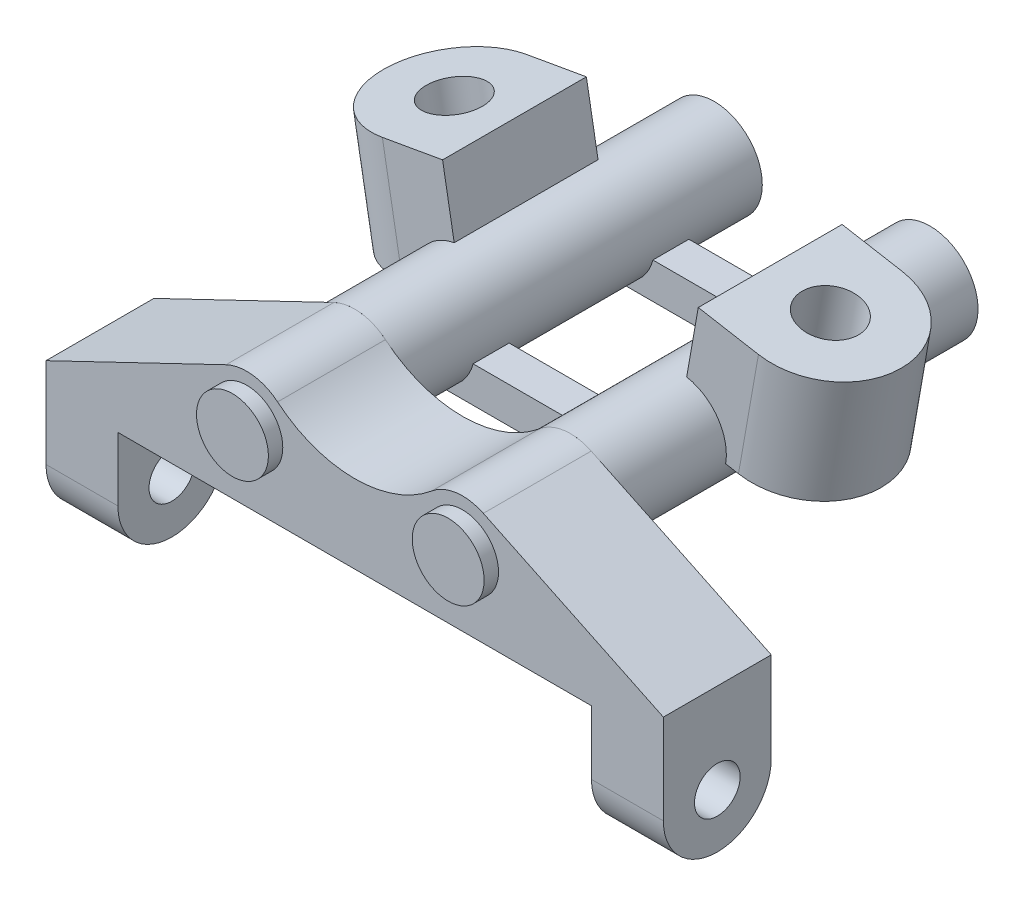
SolidWorks part; units mm, degrees
ref_plane "Front Plane" through (0, 0, 0) normal (0, 0, 1) x (1, 0, 0)
ref_plane "Top Plane" through (0, 0, 0) normal (0, 1, 0) x (1, 0, 0)
ref_plane "Right Plane" through (0, 0, 0) normal (1, 0, 0) x (0, 0, -1)
sketch "Sketch1" plane through (0, 0, 0) normal (0, 0, 1) x (1, 0, 0)
  line L0 (-42.926, -44) -> (-32.926, -44)
  line L1 (-32.926, -44) -> (-32.926, -28.7102)
  line L2 (42.926, -24) -> (42.926, -44)
  line L3 (42.926, -44) -> (32.926, -44)
  line L4 (32.926, -44) -> (32.926, -28.7102)
  line L6 (-42.926, -24) -> (-17.8935, -11.9775)
  line L7 (42.926, -24) -> (17.8912, -11.9783)
  line L8 (-42.926, -24) -> (-42.926, -44)
  line L9 (32.926, -28.7102) -> (-32.926, -28.7102)
  arc A4 (-10.7232, -12.8676) -> (10.7225, -12.8682) centre (0, 0) ccw
  arc A5 (-10.7232, -12.8676) -> (-17.8935, -11.9775) centre (-15.0008, -18.0007) ccw
  arc A6 (17.8912, -11.9783) -> (10.7225, -12.8682) centre (14.9992, -18.0007) ccw
extrude "Boss-Extrude1" add sketch "Sketch1" along normal blind 15 contours L8 L0 L1 L9 L4 L3 L2 region at (-0.0005, -25.2079, 0)
sketch "Sketch2" plane through (0, 0, 15) normal (0, 0, 1) x (1, 0, 0)
  circle A0 centre (-15.0008, -18.0007) radius 5
  circle A1 centre (14.9992, -18.0007) radius 5
extrude "Boss-Extrude2" add sketch "Sketch2" along normal blind 2
fillet "Fillet1" radius 7.5 4 edges at (37.926, -44, 0) (37.926, -44, 15) (-37.926, -44, 0) (-37.926, -44, 15)
sketch "Sketch3" plane through (42.926, 0, 0) normal (1, 0, 0) x (0, 0, -1)
  circle A0 centre (-7.5, -36.5) radius 3.175
extrude "Cut-Extrude1" cut sketch "Sketch3" against normal through all
sketch "Sketch6" plane through (0, 0, 0) normal (0, 0, -1) x (1, 0, 0)
  circle A2 centre (15, 18) radius 6.6818
  circle A3 centre (-15, 18) radius 6.6828
extrude "Boss-Extrude12" add sketch "Sketch6" along normal blind 50
ref_plane "Plane1" through (0.0008, -24.6823, 0) normal (0, -1, 0) x (-1, 0, 0)
sketch "Sketch7" plane through (0.0008, -24.6823, 0) normal (0, -1, 0) x (-1, 0, 0)
  line L0 (-15, 40) -> (15, 40)
  line L1 (15, 40) -> (15, 35)
  line L2 (15, 35) -> (-15, 35)
  line L3 (-15, 35) -> (-15, 40)
  line L4 (-15, 15) -> (-15, 10)
  line L5 (-15, 10) -> (15, 10)
  line L6 (15, 10) -> (15, 15)
  line L7 (15, 15) -> (-15, 15)
  line L9 (21.6834, 50) -> (8.3178, 50) construction
  dimension "D1" = 5
  dimension "D2" = 10
  dimension "D3" = 20
  dimension "D4" = 5
extrude "Boss-Extrude13" add sketch "Sketch7" against normal blind 5
sketch "Sketch8" plane through (0, 0, -15) normal (0, 0, -1) x (-1, 0, 0)
  line L0 (-15, -18) -> (-33.2182, -21.2124)
  line L1 (15, -18) -> (33.2182, -21.2124)
  line L4 (-35.9966, -5.4554) -> (-17.7784, -2.2431)
  line L5 (-17.7784, -2.2431) -> (-15, -18)
  line L6 (35.9966, -5.4554) -> (17.7784, -2.2431)
  line L7 (17.7784, -2.2431) -> (15, -18)
  line L8 (35.9966, -5.4554) -> (33.2182, -21.2124)
  line L9 (-35.9966, -5.4554) -> (-33.2182, -21.2124)
extrude "Boss-Extrude14" add sketch "Sketch8" along normal blind 20
sketch "Sketch9" plane through (0.1525, 0.8648, 0) normal (0.1736, 0.9848, 0) x (0.9848, -0.1736, 0)
  line L0 (26.397, 35) -> (36.397, 35)
  line L1 (36.397, 35) -> (36.397, 15)
  line L2 (36.397, 35) -> (36.397, 15) construction
  line L3 (36.397, 15) -> (26.397, 15)
  arc A0 (26.397, 15) -> (26.397, 35) centre (26.397, 25) ccw
  line M1 (17.8978, 15) -> (36.397, 15)
  line M2 (36.397, 15) -> (36.397, 35)
  line M3 (36.397, 35) -> (17.8978, 35)
extrude "Cut-Extrude2" cut sketch "Sketch9" against normal through all contours A0 L1 M3 | A0 M1 M2 region at (33.7968, -5.0676, -17.2337) region at (33.7968, -5.0676, -32.7663)
sketch "Sketch10" plane through (-0.1525, 0.8648, 0) normal (-0.1736, 0.9848, 0) x (0.9848, 0.1736, 0)
  line L0 (-26.397, 35) -> (-38.35, 35)
  line L2 (-38.35, 35) -> (-38.35, 15)
  line L4 (-38.35, 15) -> (-26.397, 15)
  arc A0 (-26.397, 35) -> (-26.397, 15) centre (-26.397, 25) ccw
  dimension "D1" = 10
extrude "Cut-Extrude3" cut sketch "Sketch10" against normal through all
sketch "Sketch14" plane through (0.1525, 0.8648, 0) normal (0.1736, 0.9848, 0) x (0.9848, -0.1736, 0)
  circle A0 centre (26.397, 25) radius 3.9688
extrude "Cut-Extrude5" cut sketch "Sketch14" against normal blind 12.7
sketch "Sketch15" plane through (-0.1525, 0.8648, 0) normal (-0.1736, 0.9848, 0) x (0.9848, 0.1736, 0)
  circle A0 centre (-26.397, 25) radius 3.9688
extrude "Cut-Extrude6" cut sketch "Sketch15" against normal blind 12.7
sketch "Sketch16" plane through (-32.926, 0, 0) normal (1, 0, 0) x (0, 0, -1)
  line L0 (-1.3021, -27.639) -> (0, -27.639)
  line L1 (-15, -27.639) -> (-13.6979, -27.639)
  line L2 (0, -27.639) -> (0, -30.25)
  line L3 (0, -24) -> (0, -36.5) construction
  line L4 (0, -30.25) -> (-15, -30.25)
  line L5 (-15, -24) -> (-15, -36.5) construction
  line L6 (-15, -30.25) -> (-15, -27.639)
  arc A0 (-1.3021, -27.639) -> (-13.6979, -27.639) centre (-7.5, -36.5) ccw
extrude "Cut-Extrude7" cut sketch "Sketch16" along normal up to surface (65.852 mm away) up to face at (32.926, -39.675, 7.5)
